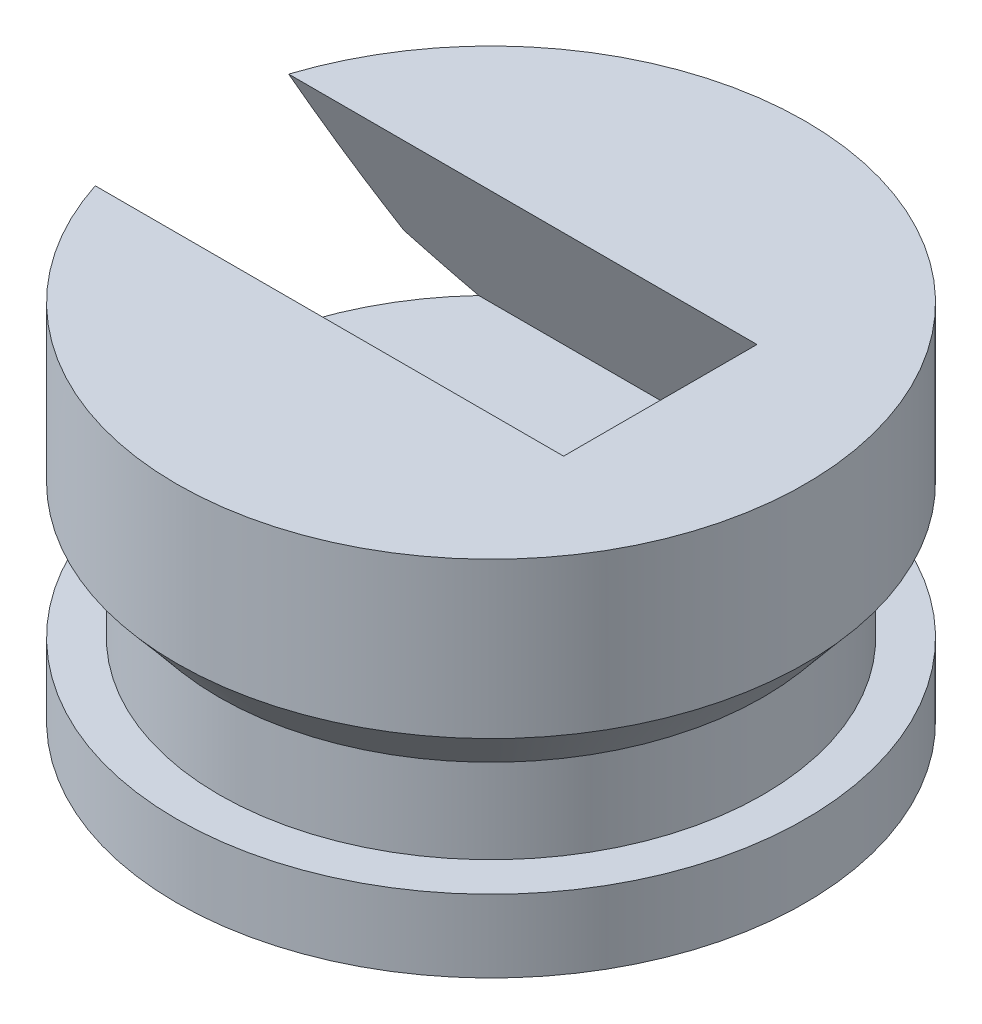
SolidWorks part; units mm, degrees
ref_plane "Front Plane" through (0, 0, 0) normal (0, 0, 1) x (1, 0, 0)
ref_plane "Top Plane" through (0, 0, 0) normal (0, 1, 0) x (1, 0, 0)
ref_plane "Side Plane" through (0, 0, 0) normal (1, 0, 0) x (0, 0, -1)
sketch "Sketch1" plane through (0, 0, 0) normal (0, 1, 0) x (1, 0, 0)
  circle A0 centre (0, 0) radius 13
  dimension "D1" = 26
extrude "Boss-Extrude1" add sketch "Sketch1" along normal blind 3
sketch "Sketch2" plane through (0, 3, 0) normal (0, 1, 0) x (1, 0, 0)
  circle A0 centre (0, 0) radius 11.25
  dimension "D1" = 22.5
extrude "Boss-Extrude2" add sketch "Sketch2" along normal blind 2
sketch "Sketch3" plane through (0, 5, 0) normal (0, 1, 0) x (1, 0, 0)
  circle A0 centre (0, 0) radius 13
  dimension "D1" = 26
extrude "Boss-Extrude4" add sketch "Sketch3" along normal blind 10
sketch "Sketch4" plane through (0, 0, 0) normal (1, 0, 0) x (0, 0, -1)
  line L0 (-11.25, 5) -> (11.25, 5) construction
  line L1 (13, 15) -> (-13, 15) construction
  line L2 (0, 7) -> (-8, 7)
  line L3 (-8, 7) -> (-4, 15)
  line L4 (-4, 15) -> (0, 15)
  line L5 (0, 7) -> (8, 7)
  line L6 (8, 7) -> (4, 15)
  line L7 (4, 15) -> (0, 15)
  dimension "D1" = 16
  dimension "D2" = 8
  dimension "D3" = 4
  dimension "D4" = 8
  dimension "D5" = 2
extrude "Cut-Extrude1" cut sketch "Sketch4" against normal through all and the other way blind 7
chamfer "Chamfer1" distance 3 angle 50 1 edges at (0, 5, 13) first distance on face at (0, 5, 13)
